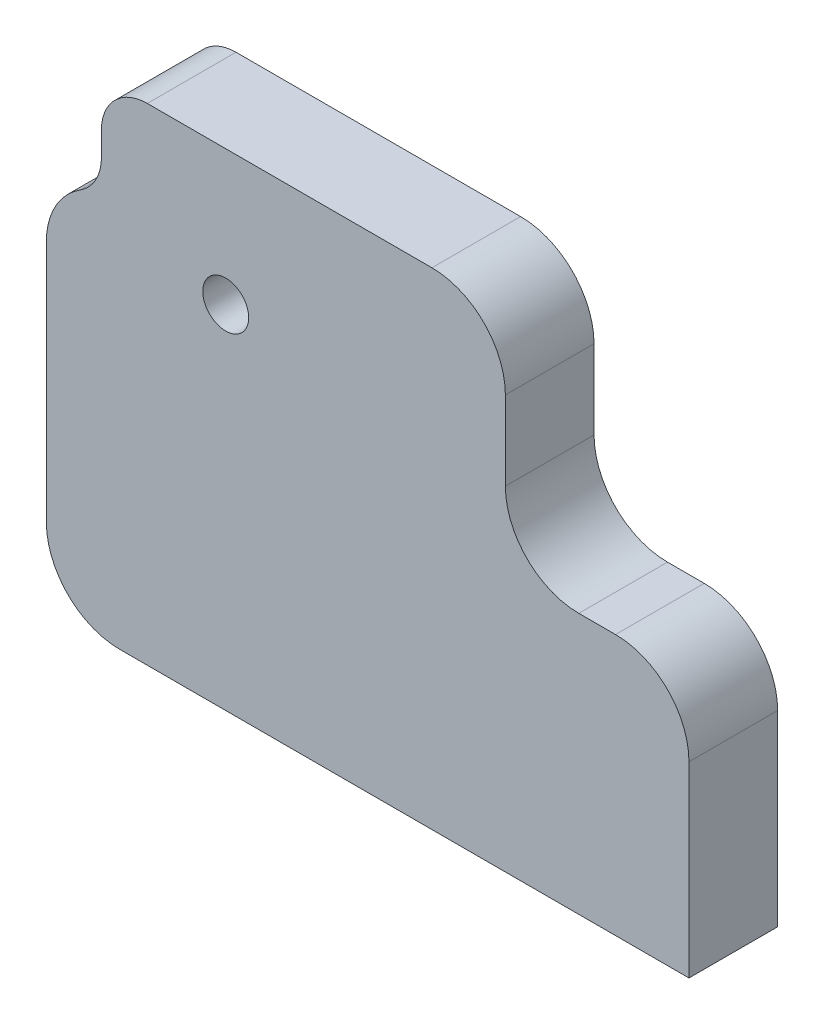
SolidWorks part; units mm, degrees
material "6061 Alloy"
ref_plane "Front" through (0, 0, 0) normal (0, 0, 1) x (1, 0, 0)
ref_plane "Top" through (0, 0, 0) normal (0, 1, 0) x (1, 0, 0)
ref_plane "Right" through (0, 0, 0) normal (1, 0, 0) x (0, 0, -1)
sketch "Sketch1" plane through (0, 0, 0) normal (0, 0, 1) x (1, 0, 0)
  line L0 (0, 0) -> (0, 15.7)
  line L9 (35, 0) -> (0, 0)
  line L15 (3, 22) -> (25, 22)
  line L16 (25, 22) -> (25, 9.7)
  line L17 (25, 9.7) -> (35, 9.7)
  line L18 (35, 9.7) -> (35, 0)
  line L20 (0, 15.7) -> (3, 15.7)
  line L21 (3, 15.7) -> (3, 22)
  dimension "D3" = 15.7
  dimension "D1" = 35
  dimension "D2" = 10
  dimension "D4" = 22
  dimension "D5" = 22
  dimension "D6" = 9.7
extrude "Boss-Extrude1" add sketch "Sketch1" along normal blind 4.83 contours L9 region at (15.5336, 9.814, 0)
hole_wizard "M3x0.5 Tapped Hole2" positions "Sketch13" profile "Sketch14" tap size "M3x0.5" standard "ANSI Metric" end condition through all
sketch "Sketch13" plane through (0, 0, 4.83) normal (0, 0, 1) x (1, 0, 0)
  line L2 (35, 0) -> (0, 0) construction
  point P5 (9.77, 14.65)
  dimension "D1" = 14.65
  dimension "D2" = 9.77
sketch "Sketch14" plane through (9.77, 14.65, 4.83) normal (1, 0, 0) x (0, -1, 0)
  line L0 (0, 0) -> (0, 4.83)
  line L1 (0, 4.83) -> (1.25, 4.83)
  line L2 (1.25, 4.83) -> (1.25, 0)
  line L5 (1.25, 0) -> (0, 0)
  line L11 (0, -6.35) -> (0, 107.95) construction
  dimension "Thru Tap Drill Dia." = 2.5
  dimension "Thru Tap Drill Depth" = 4.83
cosmetic thread "Hole Thread1" parameters "D2"=3
sketch "Sketch16" plane through (0, 0, 0) normal (0, -1, 0) x (1, 0, 0)
  line L0 (0, 4.83) -> (0, 0) construction
  line L3 (0, 2.415) -> (42.6944, 2.415) construction
  point P0 (31, 2.415)
  point P1 (19, 2.415)
  dimension "D1" = 19
  dimension "D2" = 12
hole_wizard "M3x0.5 Tapped Hole3" positions "Sketch17" profile "Sketch18" tap size "M3x0.5" standard "ANSI Metric"
sketch "Sketch17" plane through (0, 0, 0) normal (0, -1, 0) x (-1, 0, 0)
  point P0 (-19, -2.415)
  point P3 (-31, -2.415)
sketch "Sketch18" plane through (19, 0, 2.415) normal (1, 0, 0) x (0, 0, -1)
  line L0 (0, 0) -> (0, 5.7511)
  line L1 (0, 5.7511) -> (1.25, 5)
  line L2 (1.25, 5) -> (1.25, 0)
  line L5 (1.25, 0) -> (0, 0)
  line L10 (0, 5.7511) -> (-1.25, 5) construction
  line L11 (0, -6.35) -> (0, 107.95) construction
  dimension "Tap Drill Dia." = 2.5
  dimension "Tap Drill Depth" = 5
  dimension "Drill Angle" = 118
fillet "Fillet1" radius 2.5 2 edges at (3, 15.7, 2.415) (3, 22, 2.415)
chamfer "Chamfer1" [suppressed] distance 13 distance2 10
fillet "Fillet2" radius 4 4 edges at (35, 9.7, 2.415) (25, 9.7, 2.415) (25, 22, 2.415) (0, 15.7, 2.415)
sketch "Sketch20" plane through (0, 0, 0) normal (0, -1, 0) x (1, 0, 0)
  line L1 (0, 0) -> (35, 0)
  line L2 (0, 0) -> (0, 4.83)
  line L3 (0, 4.83) -> (35, 4.83)
  line L4 (35, 0) -> (35, 4.83)
  circle A0 centre (31, 2.415) radius 1.25
  circle A1 centre (19, 2.415) radius 1.25
extrude "Boss-Extrude2" add sketch "Sketch20" along normal blind 4.5
fillet "Fillet4" radius 4 1 edges at (0, -4.5, 2.415)
